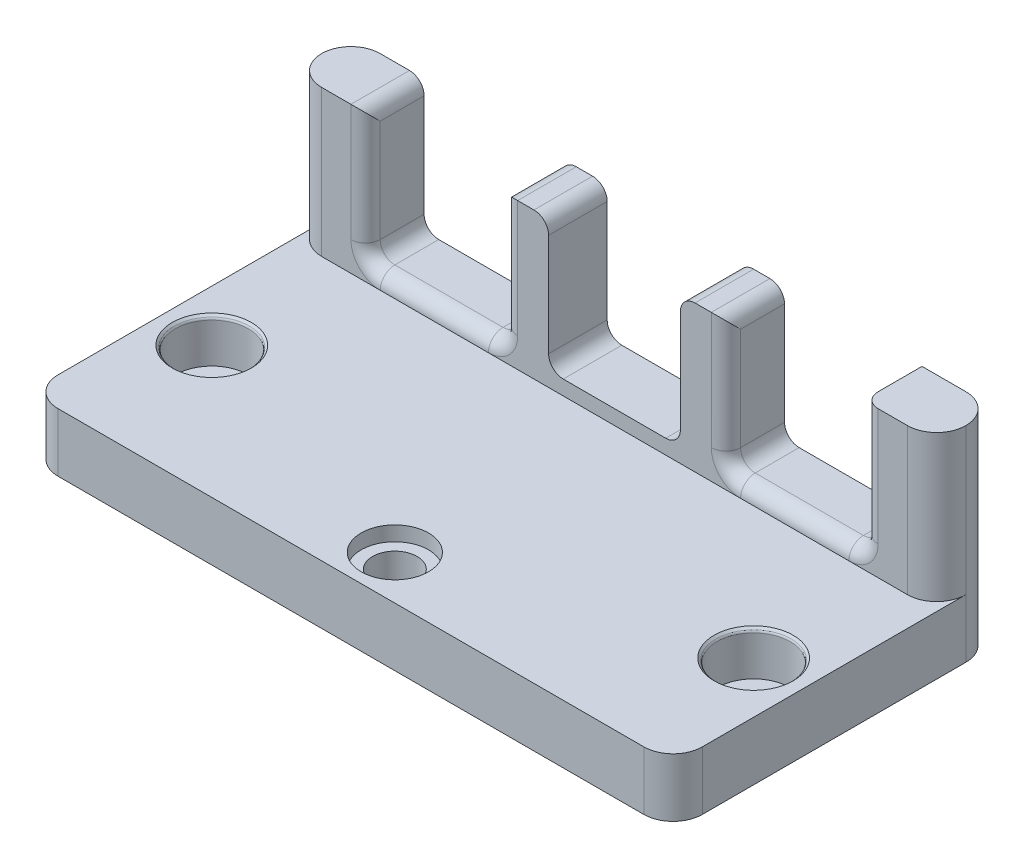
SolidWorks part; units mm, degrees
ref_plane "Front Plane" through (0, 0, 0) normal (0, 0, 1) x (1, 0, 0)
ref_plane "Top Plane" through (0, 0, 0) normal (0, 1, 0) x (1, 0, 0)
ref_plane "Right Plane" through (0, 0, 0) normal (1, 0, 0) x (0, 0, -1)
sketch "Sketch1" plane through (0, 0, 0) normal (0, 1, 0) x (1, 0, 0)
  line L1 (0, 0) -> (220, 0)
  line L2 (0, 0) -> (0, 110)
  line L3 (0, 110) -> (220, 110)
  line L4 (220, 0) -> (220, 110)
  dimension "D1" = 220
  dimension "D2" = 110
extrude "Boss-Extrude1" add sketch "Sketch1" along normal blind 20
sketch "Sketch2" plane through (0, 20, 0) normal (0, 1, 0) x (1, 0, 0)
  line L0 (0, 45) -> (220, 45) construction
  line L1 (0, 110) -> (0, 0) construction
  line L2 (220, 0) -> (220, 110) construction
  line L3 (0, 0) -> (220, 0) construction
  line L4 (110, 45) -> (110, 110) construction
  line L5 (220, 110) -> (0, 110) construction
  circle A0 centre (17.5, 45) radius 12.5
  circle A1 centre (202.5, 45) radius 12.5
  circle A2 centre (110, 15) radius 7.6
  point P10 (110, 45)
  dimension "D2" = 25
  dimension "D4" = 15
  dimension "D5" = 15.2
  dimension "D1" = 45
  dimension "D3" = 92.5
extrude "Cut-Extrude1" cut sketch "Sketch2" against normal blind 15
sketch "Sketch3" plane through (0, 20, 0) normal (0, 1, 0) x (1, 0, 0)
  line L0 (220, 0) -> (220, 110) construction
  line L1 (0, 110) -> (220, 110)
  line L2 (0, 110) -> (0, 90)
  line L3 (0, 90) -> (220, 90)
  line L4 (220, 110) -> (220, 90)
  dimension "D1" = 20
extrude "Boss-Extrude2" add sketch "Sketch3" along normal blind 50
chamfer "Chamfer1" distance 1 angle 45 2 edges at (202.5, 20, -57.5) (17.5, 20, -32.5)
fillet "Fillet1" radius 1 2 edges at (202.5, 19, -57.5) (17.5, 19, -57.5)
fillet "Fillet2" radius 10 6 edges at (220, 45, -90) (0, 45, -90) (0, 35, -110) (0, 10, 0) (220, 35, -110) (220, 10, 0)
sketch "Sketch4" plane through (0, 20, 0) normal (0, 1, 0) x (1, 0, 0)
  circle A0 centre (110, 15) radius 11.5
  dimension "D1" = 23
extrude "Cut-Extrude2" cut sketch "Sketch4" against normal blind 5
sketch "Sketch5" plane through (0, 0, -110) normal (0, 0, -1) x (-1, 0, 0)
  line L0 (-195, 70) -> (-25, 70)
  line L1 (-210, 70) -> (-10, 70) construction
  line L2 (-110, 70) -> (-110, 27.057) construction
  line L7 (-195, 70) -> (-195, 0) construction
  line L8 (-210, 0) -> (-10, 0) construction
  line L9 (-25, 70) -> (-25, 0) construction
  line L10 (-195, 85) -> (-148.0592, 85)
  line L11 (-25, 25) -> (-71.9408, 25)
  line L12 (-25, 25) -> (-25, 85)
  line L13 (-25, 85) -> (-71.9408, 85)
  line L14 (-71.9408, 25) -> (-71.9408, 85)
  line L15 (-148.0592, 25) -> (-148.0592, 85)
  line L16 (-195, 25) -> (-148.0592, 25)
  line L17 (-195, 25) -> (-195, 85)
  line L19 (-132.5, 115) -> (-87.5, 115)
  line L20 (-132.5, 115) -> (-132.5, 25)
  line L21 (-132.5, 25) -> (-87.5, 25)
  line L22 (-87.5, 115) -> (-87.5, 25)
  line L23 (-132.5, 115) -> (-87.5, 25) construction
  line L24 (-132.5, 25) -> (-87.5, 115) construction
  point P5 (-110, 70)
  dimension "D1" = 170
  dimension "D2" = 46.9408
  dimension "D3" = 60
  dimension "D4" = 15
  dimension "D5" = 45
  dimension "D6" = 90
extrude "Cut-Extrude3" cut sketch "Sketch5" against normal through all contours L10 L15 L16 L17 | L20 L19 L22 L21 | L12 L11 L14 L13
fillet "Fillet4" radius 5 17 edges at (195, 47.5, -90) (148.0592, 47.5, -90) (25, 47.5, -90) (71.9408, 47.5, -90) (171.5296, 25, -90) (48.4704, 25, -90) (25, 70, -100) (25, 25, -100) (71.9408, 25, -100) (71.9408, 70, -100) (87.5, 70, -100) (87.5, 25, -100) (132.5, 25, -100) (132.5, 70, -100) (148.0592, 70, -100) (148.0592, 25, -100) (195, 25, -100)
sketch "Sketch6" plane through (0, 0, -110) normal (0, 0, -1) x (-1, 0, 0)
  line L0 (-110, 25) -> (-110, 0) construction
  line L1 (-127.5, 25) -> (-92.5, 25) construction
  line L2 (-210, 0) -> (-10, 0) construction
  circle A0 centre (-110, 12.5) radius 3.2
  dimension "D1" = 6.4
extrude "Cut-Extrude4" cut sketch "Sketch6" against normal blind 10
